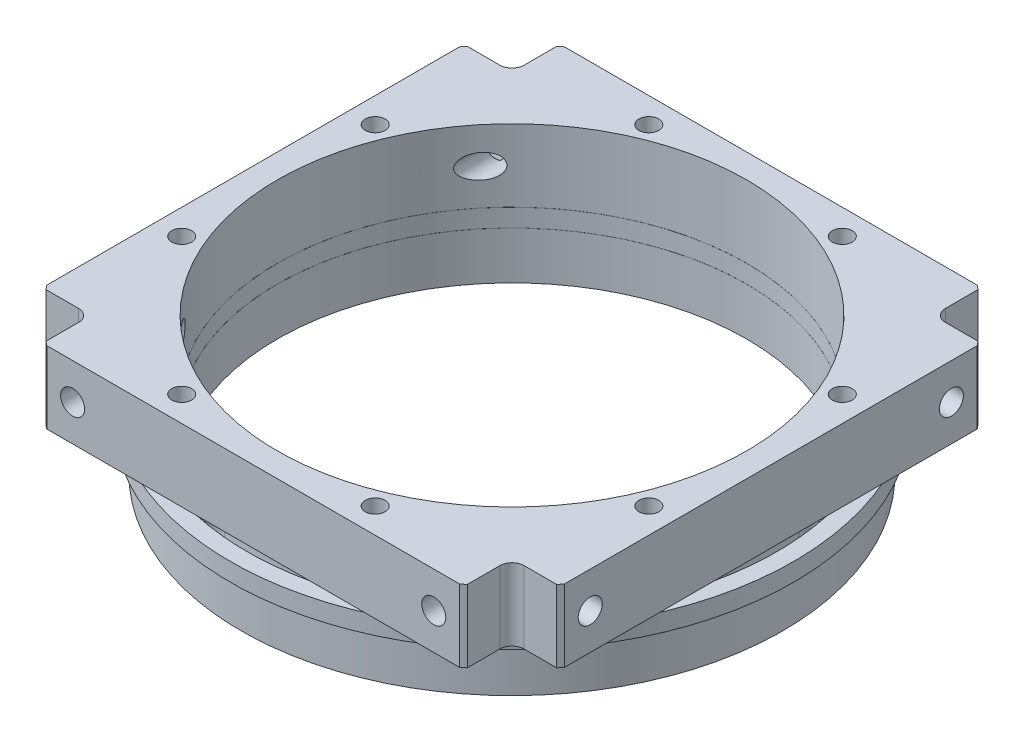
SolidWorks part; units mm, degrees
material "6061-T6 (SS)"
ref_plane "前视基准面" through (0, 0, 0) normal (0, 0, 1) x (1, 0, 0)
ref_plane "上视基准面" through (0, 0, 0) normal (0, 1, 0) x (1, 0, 0)
ref_plane "右视基准面" through (0, 0, 0) normal (1, 0, 0) x (0, 0, -1)
sketch "草图1" plane through (0, 0, 0) normal (0, 0, 1) x (1, 0, 0)
  line L0 (0, 0) -> (0, 30.5389) construction
  line L1 (-39, 0) -> (-45, 0)
  line L2 (-45, 0) -> (-45, 7.9)
  line L3 (-45, 7.9) -> (-46.8, 7.9)
  line L4 (-46.8, 7.9) -> (-46.8, 10.9)
  line L5 (-46.8, 10.9) -> (-55, 10.9)
  line L6 (-55, 10.9) -> (-55, 22.9)
  line L7 (-55, 22.9) -> (-39, 22.9)
  line L10 (-39, 22.9) -> (-39, 0)
  dimension "D1" = 90
  dimension "D2" = 78
  dimension "D3" = 7.9
  dimension "D4" = 1.8
  dimension "D5" = 3
  dimension "D6" = 110
  dimension "D9" = 12
revolve "旋转1" add sketch "草图1" angle 360 about L0
sketch "草图2" plane through (0, 22.9, 0) normal (0, 1, 0) x (1, 0, 0)
  line L1 (43, -43) -> (-43, -43)
  line L2 (43, -43) -> (43, 43)
  line L3 (43, 43) -> (-43, 43)
  line L4 (-43, -43) -> (-43, 43)
  line L5 (43, -43) -> (-43, 43) construction
  line L6 (43, 43) -> (-43, -43) construction
  point P0 (0, 0)
  dimension "D1" = 86
extrude "切除-拉伸1" cut sketch "草图2" against normal up to surface (12 mm away) flip side to cut up to face at (0, 10.9, -46.8)
sketch "草图4" plane through (0, 0, 43) normal (0, 0, 1) x (1, 0, 0)
  line L0 (-30, 16.9) -> (30, 16.9) construction
  line L1 (0, 16.9) -> (0, 0) construction
  line L3 (34.2929, 10.9) -> (18.4727, 10.9) construction
  circle A0 centre (-30, 16.9) radius 2
  circle A1 centre (30, 16.9) radius 2
  dimension "D3" = 4
  dimension "D1" = 6
  dimension "D2" = 60
extrude "切除-拉伸3" cut sketch "草图4" against normal through all
cosmetic thread "装饰螺纹线3" parameters "D2"=5
cosmetic thread "装饰螺纹线4" parameters "D2"=5
cosmetic thread "装饰螺纹线7" parameters "D2"=5
cosmetic thread "装饰螺纹线8" parameters "D2"=5
sketch "草图5" plane through (-43, 0, 0) normal (-1, 0, 0) x (0, 0, 1)
  line L0 (0, 0) -> (0, 16.9) construction
  line L1 (-30, 16.9) -> (30, 16.9) construction
  line L2 (34.2929, 10.9) -> (18.4727, 10.9) construction
  circle A0 centre (-30, 16.9) radius 2
  circle A1 centre (30, 16.9) radius 2
  dimension "D3" = 4
  dimension "D1" = 6
  dimension "D2" = 60
extrude "切除-拉伸4" cut sketch "草图5" against normal blind 12
cosmetic thread "装饰螺纹线5" parameters "D2"=5
cosmetic thread "装饰螺纹线6" parameters "D2"=5
extrude "切除-拉伸5" cut sketch "草图5<2>" along normal blind 12 from surface starting at face at (43, 14.9, 0)
sketch "草图5<2>" plane through (-43, 0, 0) normal (-1, 0, 0) x (0, 0, 1) same geometry as "草图5"
cosmetic thread "装饰螺纹线1" parameters "D2"=5
cosmetic thread "装饰螺纹线2" parameters "D2"=5
sketch "草图6" plane through (0, 0, 0) normal (0, -1, 0) x (1, 0, 0)
  line L0 (0, 0) -> (-16.0727, -38.8029) construction
  line L1 (0, 0) -> (0, -42) construction
  circle A0 centre (0, 0) radius 42 construction
  circle A1 centre (-16.0727, -38.8029) radius 1.65
  dimension "D1" = 84
  dimension "D2" = 3.3
  dimension "D3" = 22.5
extrude "切除-拉伸6" cut sketch "草图6" against normal blind 100
cosmetic thread "装饰螺纹线9" parameters "D2"=4
sketch "草图10" plane through (0, 0, 0) normal (0, -1, 0) x (1, 0, 0)
  circle A0 centre (-16.0727, -38.8029) radius 2.1
  dimension "D1" = 4.2
extrude "切除-拉伸8" cut sketch "草图10" against normal up to surface (10.9 mm away) up to face at (-35.3416, 10.9, -35.3416)
pattern_circular "阵列(圆周)1" count 8 over 360 about axis through (0, 0, 0) along (0, -1, 0) of "切除-拉伸6", "切除-拉伸8" reverse direction yes
sketch "草图7" plane through (0, 22.9, 0) normal (0, 1, 0) x (1, 0, 0)
  line L1 (35, -35) -> (-35, -35) construction
  line L2 (35, -35) -> (35, 35) construction
  line L3 (35, 35) -> (-35, 35) construction
  line L4 (-35, -35) -> (-35, 35) construction
  line L5 (35, -35) -> (-35, 35) construction
  line L6 (35, 35) -> (-35, -35) construction
  line L7 (-37, 35) -> (-53, 35)
  line L8 (-35, 37) -> (-35, 53)
  line L9 (-37, 55) -> (-53, 55)
  line L10 (-55, 37) -> (-55, 53)
  line L11 (37, 35) -> (53, 35)
  line L12 (35, 37) -> (35, 53)
  line L13 (37, 55) -> (53, 55)
  line L14 (55, 37) -> (55, 53)
  line L15 (37, -35) -> (53, -35)
  line L16 (35, -37) -> (35, -53)
  line L17 (37, -55) -> (53, -55)
  line L18 (55, -37) -> (55, -53)
  line L19 (-37, -35) -> (-53, -35)
  line L20 (-35, -37) -> (-35, -53)
  line L21 (-37, -55) -> (-53, -55)
  line L22 (-55, -37) -> (-55, -53)
  arc A0 (-53, -35) -> (-55, -37) centre (-53, -37) ccw
  arc A1 (-35, -53) -> (-37, -55) centre (-37, -53) cw
  arc A2 (-53, -55) -> (-55, -53) centre (-53, -53) cw
  arc A3 (53, -35) -> (55, -37) centre (53, -37) cw
  arc A4 (35, -53) -> (37, -55) centre (37, -53) ccw
  arc A5 (53, -55) -> (55, -53) centre (53, -53) ccw
  arc A6 (53, 35) -> (55, 37) centre (53, 37) ccw
  arc A7 (35, 53) -> (37, 55) centre (37, 53) cw
  arc A8 (53, 55) -> (55, 53) centre (53, 53) cw
  arc A9 (-53, 35) -> (-55, 37) centre (-53, 37) cw
  arc A10 (-35, 53) -> (-37, 55) centre (-37, 53) ccw
  arc A11 (-53, 55) -> (-55, 53) centre (-53, 53) ccw
  arc A12 (-37, -35) -> (-35, -37) centre (-37, -37) cw
  arc A13 (37, 35) -> (35, 37) centre (37, 37) cw
  arc A14 (35, -37) -> (37, -35) centre (37, -37) cw
  arc A15 (-35, 37) -> (-37, 35) centre (-37, 37) cw
  point P0 (0, 0)
  point P32 (55, 35)
  point P37 (55, 55)
  dimension "D3" = 2
  dimension "D1" = 70
  dimension "D2" = 20
extrude "切除-拉伸7" cut sketch "草图7" against normal blind 20
sketch "草图11" plane through (0, 0, 0) normal (1, 0, 0) x (0, 0, -1)
  line L0 (-45, 7.9) -> (45, 7.9) construction
  line L1 (-74.0955, 7.9) -> (62.1019, 7.9)
  line L2 (-74.0955, 7.9) -> (-74.0955, 7.89)
  line L3 (-74.0955, 7.89) -> (62.1019, 7.89)
  line L4 (62.1019, 7.9) -> (62.1019, 7.89)
  line L5 (-74.0955, 10.9) -> (62.1019, 10.9)
  line L6 (-74.0955, 10.9) -> (-74.0955, 10.89)
  line L7 (-74.0955, 10.89) -> (62.1019, 10.89)
  line L8 (62.1019, 10.9) -> (62.1019, 10.89)
  line L9 (18.4727, 10.9) -> (-18.4727, 10.9) construction
  dimension "D1" = 0.01
extrude "板材方案切割" cut sketch "草图11" against normal through all both and the other way through all
sketch "草图12" plane through (0, 0, 0) normal (0, -1, 0) x (1, 0, 0)
  line L0 (-9.0905, 41.0044) -> (0, 0) construction
  line L1 (0, 0) -> (9.0905, 41.0044) construction
  line L2 (0, 42) -> (0, 0) construction
  circle A0 centre (0, 0) radius 42 construction
  arc A1 (-9.0905, 41.0044) -> (9.0905, 41.0044) centre (0, 0) cw construction
  arc A2 (9.5233, 42.957) -> (-9.5233, 42.957) centre (0, 0) ccw
  arc A3 (8.6576, 39.0518) -> (-8.6576, 39.0518) centre (0, 0) ccw
  arc A4 (8.6576, 39.0518) -> (9.5233, 42.957) centre (9.0905, 41.0044) ccw
  arc A5 (-9.5233, 42.957) -> (-8.6576, 39.0518) centre (-9.0905, 41.0044) ccw
  arc A6 (22.5666, 35.4224) -> (35.4224, 22.5666) centre (0, 0) cw construction
  arc A7 (37.1092, 23.6412) -> (23.6412, 37.1092) centre (0, 0) ccw
  arc A8 (33.7357, 21.492) -> (21.492, 33.7357) centre (0, 0) ccw
  arc A9 (33.7357, 21.492) -> (37.1092, 23.6412) centre (35.4224, 22.5666) ccw
  arc A10 (23.6412, 37.1092) -> (21.492, 33.7357) centre (22.5666, 35.4224) ccw
  arc A11 (41.0044, 9.0905) -> (41.0044, -9.0905) centre (0, 0) cw construction
  arc A12 (42.957, -9.5233) -> (42.957, 9.5233) centre (0, 0) ccw
  arc A13 (39.0518, -8.6576) -> (39.0518, 8.6576) centre (0, 0) ccw
  arc A14 (39.0518, -8.6576) -> (42.957, -9.5233) centre (41.0044, -9.0905) ccw
  arc A15 (42.957, 9.5233) -> (39.0518, 8.6576) centre (41.0044, 9.0905) ccw
  arc A16 (35.4224, -22.5666) -> (22.5666, -35.4224) centre (0, 0) cw construction
  arc A17 (23.6412, -37.1092) -> (37.1092, -23.6412) centre (0, 0) ccw
  arc A18 (21.492, -33.7357) -> (33.7357, -21.492) centre (0, 0) ccw
  arc A19 (21.492, -33.7357) -> (23.6412, -37.1092) centre (22.5666, -35.4224) ccw
  arc A20 (37.1092, -23.6412) -> (33.7357, -21.492) centre (35.4224, -22.5666) ccw
  arc A21 (9.0905, -41.0044) -> (-9.0905, -41.0044) centre (0, 0) cw construction
  arc A22 (-9.5233, -42.957) -> (9.5233, -42.957) centre (0, 0) ccw
  arc A23 (-8.6576, -39.0518) -> (8.6576, -39.0518) centre (0, 0) ccw
  arc A24 (-8.6576, -39.0518) -> (-9.5233, -42.957) centre (-9.0905, -41.0044) ccw
  arc A25 (9.5233, -42.957) -> (8.6576, -39.0518) centre (9.0905, -41.0044) ccw
  arc A26 (-22.5666, -35.4224) -> (-35.4224, -22.5666) centre (0, 0) cw construction
  arc A27 (-37.1092, -23.6412) -> (-23.6412, -37.1092) centre (0, 0) ccw
  arc A28 (-33.7357, -21.492) -> (-21.492, -33.7357) centre (0, 0) ccw
  arc A29 (-33.7357, -21.492) -> (-37.1092, -23.6412) centre (-35.4224, -22.5666) ccw
  arc A30 (-23.6412, -37.1092) -> (-21.492, -33.7357) centre (-22.5666, -35.4224) ccw
  arc A31 (-41.0044, -9.0905) -> (-41.0044, 9.0905) centre (0, 0) cw construction
  arc A32 (-42.957, 9.5233) -> (-42.957, -9.5233) centre (0, 0) ccw
  arc A33 (-39.0518, 8.6576) -> (-39.0518, -8.6576) centre (0, 0) ccw
  arc A34 (-39.0518, 8.6576) -> (-42.957, 9.5233) centre (-41.0044, 9.0905) ccw
  arc A35 (-42.957, -9.5233) -> (-39.0518, -8.6576) centre (-41.0044, -9.0905) ccw
  arc A36 (-35.4224, 22.5666) -> (-22.5666, 35.4224) centre (0, 0) cw construction
  arc A37 (-23.6412, 37.1092) -> (-37.1092, 23.6412) centre (0, 0) ccw
  arc A38 (-21.492, 33.7357) -> (-33.7357, 21.492) centre (0, 0) ccw
  arc A39 (-21.492, 33.7357) -> (-23.6412, 37.1092) centre (-22.5666, 35.4224) ccw
  arc A40 (-37.1092, 23.6412) -> (-33.7357, 21.492) centre (-35.4224, 22.5666) ccw
  point P6 (0, 42)
  point P20 (29.6985, 29.6985)
  point P27 (42, 0)
  point P34 (29.6985, -29.6985)
  point P41 (0, -42)
  point P48 (-29.6985, -29.6985)
  point P55 (-42, 0)
  point P62 (-29.6985, 29.6985)
  point P67 (0, 0)
  dimension "D2" = 2
  dimension "D1" = 25
  dimension "D3" = 8
extrude "切除-拉伸9" cut sketch "草图12" against normal through all
